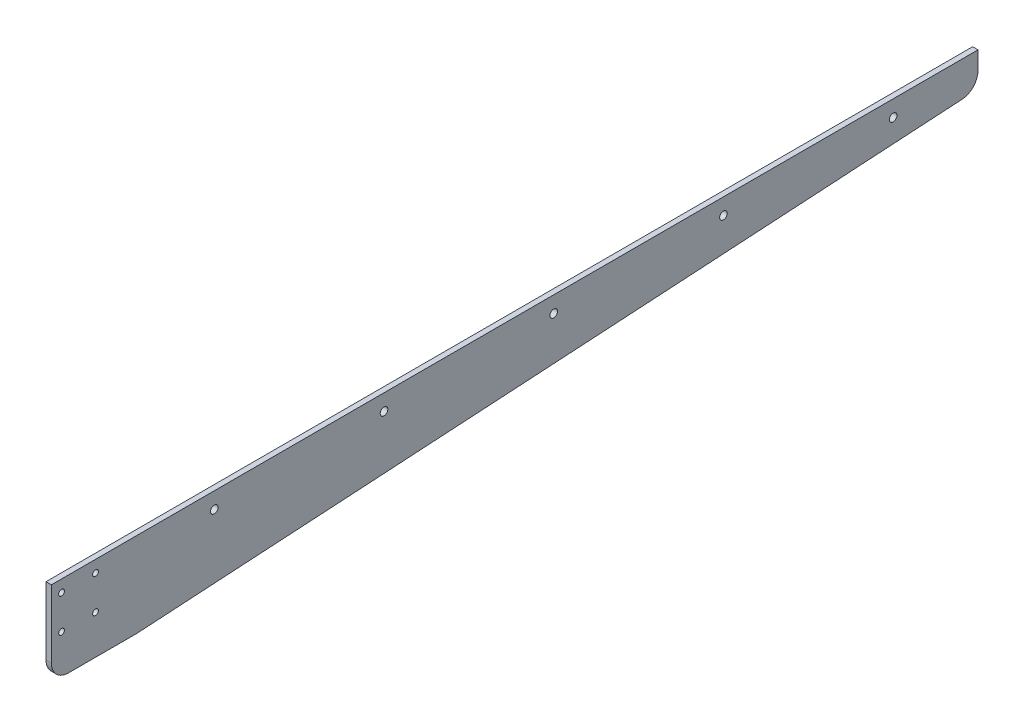
SolidWorks part; units mm, degrees
ref_plane "Front Plane" through (0, 0, 0) normal (0, 0, 1) x (1, 0, 0)
ref_plane "Top Plane" through (0, 0, 0) normal (0, 1, 0) x (1, 0, 0)
ref_plane "Right Plane" through (0, 0, 0) normal (1, 0, 0) x (0, 0, -1)
sketch "Sketch1" plane through (0, 0, 0) normal (1, 0, 0) x (0, 0, -1)
  line L0 (0, 0) -> (0, 50)
  line L1 (546, 50) -> (546, 30)
  line L2 (546, 30) -> (50, 0)
  line L3 (50, 0) -> (0, 0)
  line L4 (0, 50) -> (546, 50)
  dimension "D1" = 546
  dimension "D2" = 50
  dimension "D3" = 50
  dimension "D4" = 20
extrude "Boss-Extrude1" add sketch "Sketch1" along normal blind 3.175
hole_wizard "M3 Clearance Hole1" positions "3DSketch1" profile "Sketch3" hole size "M3" standard "ANSI Metric" end condition through all
sketch3d "3DSketch1"
  line L0 (3.175, 50, -6) -> (3.175, 0, -6) construction
  line L1 (3.175, 50, -546) -> (3.175, 50, 0) construction
  line L2 (3.175, 0, 0) -> (3.175, 0, -50) construction
  line L3 (3.175, 0, -26) -> (3.175, 50, -26) construction
  line L4 (3.175, 50, 0) -> (3.175, 0, 0) construction
  line L5 (3.175, 43, -6) -> (3.175, 23, -6) construction
  point P0 (3.175, 43, -26)
  point P11 (3.175, 43, -6)
  point P13 (3.175, 23, -26)
  point P15 (3.175, 23, -6)
  dimension "D1" = 20
  dimension "D2" = 20
  dimension "D3" = 6
  dimension "D4" = 7
sketch "Sketch3" plane through (3.175, 43, -26) normal (0, 1, 0) x (0, 0, -1)
  line L0 (0, 0) -> (0, 3.175)
  line L1 (0, 3.175) -> (1.7, 3.175)
  line L2 (1.7, 3.175) -> (1.7, 0)
  line L5 (1.7, 0) -> (0, 0)
  line L11 (0, -6.35) -> (0, 107.95) construction
  dimension "Thru Hole Dia." = 3.4
  dimension "Thru Hole Depth" = 3.175
fillet "Fillet1" radius 10 3 edges at (1.5875, 0, -50) (1.5875, 0, 0) (1.5875, 30, -546)
hole_wizard "#8 Clearance Hole1" positions "3DSketch2" profile "Sketch4" hole size "#8" standard "ANSI Inch" end condition through all
sketch3d "3DSketch2"
  line L0 (3.175, 39.4134, -546) -> (3.175, 50, -546) construction
  line L1 (3.175, 50, -546) -> (3.175, 50, 0) construction
  point P0 (3.175, 40.475, -496)
  dimension "D1" = 50
  dimension "D2" = 9.525
sketch "Sketch4" plane through (3.175, 40.475, -496) normal (0, 1, 0) x (0, 0, -1)
  line L0 (0, 0) -> (0, 3.175)
  line L1 (0, 3.175) -> (2.2479, 3.175)
  line L2 (2.2479, 3.175) -> (2.2479, 0)
  line L5 (2.2479, 0) -> (0, 0)
  line L11 (0, -6.35) -> (0, 107.95) construction
  dimension "Thru Hole Dia." = 4.4958
  dimension "Thru Hole Depth" = 3.175
pattern_linear "LPattern1" count 5 spacing 100 along (0, 0, 1) of "#8 Clearance Hole1"
